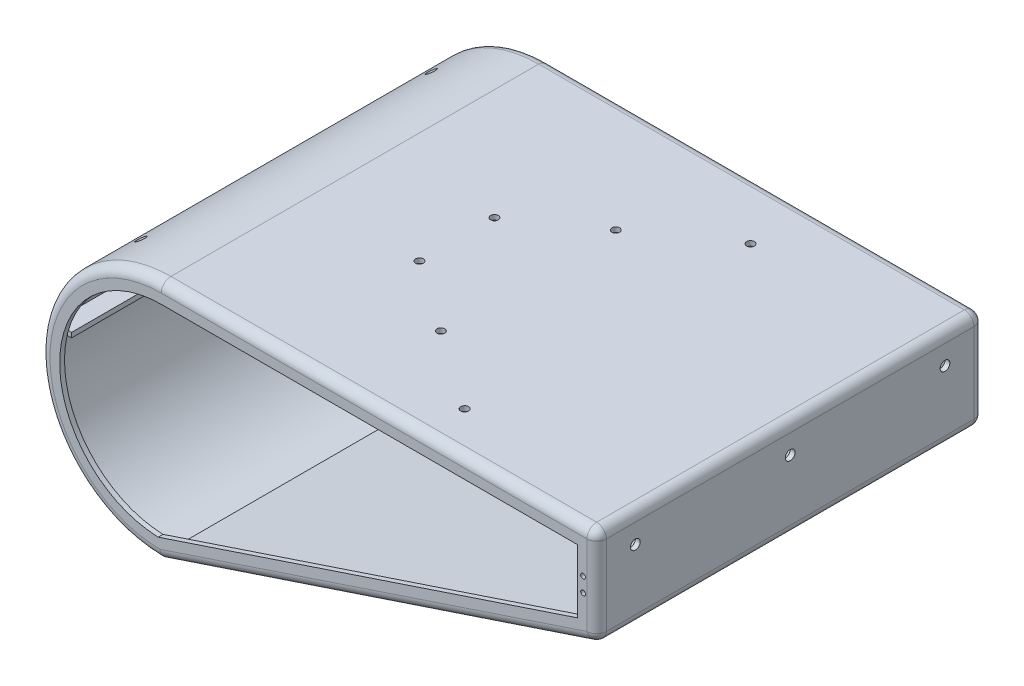
SolidWorks part; units mm, degrees
material "Acrylic (Medium-high impact)"
ref_plane "Front Plane" through (0, 0, 0) normal (0, 0, 1) x (1, 0, 0)
ref_plane "Top Plane" through (0, 0, 0) normal (0, 1, 0) x (1, 0, 0)
ref_plane "Right Plane" through (0, 0, 0) normal (1, 0, 0) x (0, 0, -1)
sketch "Sketch1" plane through (0, 0, 0) normal (0, 0, 1) x (1, 0, 0)
  line L1 (-100, 0) -> (350, 0)
  line L4 (350, 0) -> (350, -100)
  line L5 (-100, -250) -> (350, -100)
  arc A0 (-100, 0) -> (-100, -250) centre (-100, -125) ccw
  dimension "D2" = 125
  dimension "D1" = 350
  dimension "D3" = 100
  dimension "D4" = 100
extrude "Boss-Extrude1" add sketch "Sketch1" along normal blind 400 contours L1 L4 L5 A0
fillet "Fillet1" radius 10 10 edges at (-225, -125, 0) (-225, -125, 400) (125, 0, 0) (125, -175, 0) (350, -50, 0) (350, -100, 200) (350, 0, 200) (350, -50, 400) (125, -175, 400) (125, 0, 400)
ref_plane "Plane2" through (0, 0, 5) normal (0, 0, -1) x (-1, 0, 0)
sketch "Sketch7" plane through (0, 0, 5) normal (0, 0, -1) x (-1, 0, 0)
  line L9 (-345, -96.3962) -> (100.8033, -244.9973)
  line L10 (-345, -5) -> (-345, -96.3962)
  line L11 (100, -5) -> (-345, -5)
  line L12 (-345, -96.3962) -> (100.8033, -244.9973)
  line L13 (-345, -5) -> (-345, -96.3962)
  line L14 (100, -5) -> (-345, -5)
  arc A5 (100.8033, -244.9973) -> (100, -5) centre (100, -125) ccw
  arc A6 (100.8033, -244.9973) -> (100, -5) centre (100, -125) ccw
  dimension "D1" = 5
sketch "Sketch4" plane through (350, 0, 0) normal (1, 0, 0) x (0, 0, -1)
  line L0 (-390, -30) -> (-10, -30) construction
  line L4 (-10, -10) -> (-390, -10) construction
  line L5 (-390, -10) -> (-390, -92.7924) construction
  line L6 (-10, -92.7924) -> (-10, -10) construction
  circle A0 centre (-200, -30) radius 5
  circle A1 centre (-360, -30) radius 5
  circle A2 centre (-40, -30) radius 5
  dimension "D1" = 10
  dimension "D2" = 20
  dimension "D3" = 30
  dimension "D4" = 30
sketch "Sketch6" plane through (0, 0, 0) normal (0, 1, 0) x (1, 0, 0)
  line L3 (-37.2545, -10) -> (-37.2545, -390) construction
  line L4 (340, -10) -> (-100, -10) construction
  line L5 (-100, -390) -> (340, -390) construction
  arc A0 (8.0546, -173.8432) -> (7.7455, -225.9808) centre (22.7455, -200) ccw construction
  circle A3 centre (88.3792, -118.6576) radius 4
  circle A4 centre (88.3792, -299.4355) radius 4
  circle A5 centre (14.6483, -170.2692) radius 4
  circle A6 centre (14.6483, -247.8239) radius 4
  circle A7 centre (170.3024, -356.7817) radius 4
  circle A8 centre (170.3024, -61.3114) radius 4
  circle A9 centre (14.6483, -247.8239) radius 2.5 construction
  circle A10 centre (88.3792, -118.6576) radius 2.5 construction
  circle A11 centre (88.3792, -299.4355) radius 2.5 construction
  circle A12 centre (170.3024, -356.7817) radius 2.5 construction
  circle A13 centre (170.3024, -61.3114) radius 2.5 construction
  point P18 (22.7455, -200)
  dimension "D6" = 8
  dimension "D1" = 170.2692
  dimension "D7" = 7.5
extrude "Cut-Extrude1" cut sketch "Sketch7" against normal blind 390
sketch "Sketch8" plane through (0, 0, 400) normal (0, 0, 1) x (1, 0, 0)
  line L6 (-103.1076, -229.954) -> (330, -85.5848)
  line L7 (330, -85.5848) -> (330, -20)
  line L8 (330, -20) -> (-100, -20)
  line L9 (-103.1076, -229.954) -> (330, -85.5848)
  line L10 (330, -85.5848) -> (330, -20)
  line L11 (330, -20) -> (-100, -20)
  arc A2 (-100, -20) -> (-103.1076, -229.954) centre (-100, -125) ccw
  arc A3 (-100, -20) -> (-103.1076, -229.954) centre (-100, -125) ccw
  dimension "D1" = 10
extrude "Cut-Extrude2" cut sketch "Sketch8" against normal blind 10
extrude "Cut-Extrude3" cut sketch "Sketch6" against normal blind 10
sketch "Sketch9" plane through (0, 0, 5) normal (0, 0, -1) x (-1, 0, 0)
  line L0 (-345, -96.3962) -> (216.5411, -96.3962) construction
  line L1 (216.5411, -96.3962) -> (197.6557, -96.3962)
  line L2 (197.6557, -96.3962) -> (197.6557, -101.3962)
  line L3 (197.6557, -101.3962) -> (217.6557, -101.3962)
  line L5 (-325, -96.3962) -> (-325, -103.0629)
  line L6 (-345, -96.3962) -> (100.8033, -244.9973) construction
  line L7 (-325, -96.3962) -> (-345, -96.3962)
  line L8 (-345, -96.3962) -> (-325, -103.0629)
  line L10 (216.5411, -96.3962) -> (218.5411, -96.3962)
  line L11 (218.5411, -96.3962) -> (218.5411, -101.3962)
  line L12 (218.5411, -101.3962) -> (217.6557, -101.3962)
  arc A0 (100.8033, -244.9973) -> (100, -5) centre (100, -125) ccw construction
  dimension "D1" = 5
  dimension "D2" = 20
  dimension "D3" = 20
  dimension "D4" = 2
extrude "Boss-Extrude2" add sketch "Sketch9" against normal blind 390
extrude "Cut-Extrude4" cut sketch "Sketch4" against normal blind 10
sketch "Sketch10" plane through (0, 0, 400) normal (0, 0, 1) x (1, 0, 0)
  line L0 (330, -85.5848) -> (330, -20) construction
  line L1 (336, -45.2924) -> (336, -60.2924) construction
  line L2 (330, -20) -> (330, -85.5848) construction
  circle A0 centre (336, -45.2924) radius 2.5
  circle A1 centre (336, -60.2924) radius 2.5
  point P13 (330, -52.7924)
  point P14 (336, -52.7924)
  dimension "D1" = 5
  dimension "D2" = 15
  dimension "D3" = 6
extrude "Cut-Extrude5" cut sketch "Sketch10" against normal blind 10
sketch "Sketch11" plane through (0, 0, 400) normal (0, 0, 1) x (1, 0, 0)
  line L0 (-225, -125) -> (-100, -125) construction
  arc A1 (-100, 0) -> (-100, -250) centre (-100, -125) ccw construction
ref_plane "Plane3" through (-45.8653, 65.5024, 0) normal (-0.5736, 0.8192, 0) x (0, 0, -1)
sketch "Sketch12" plane through (-45.8653, 65.5024, 0) normal (-0.5736, 0.8192, 0) x (0, 0, -1)
  line L0 (-390, 81.9152) -> (-10, 81.9152) construction
  line L1 (-350, 152.8988) -> (-50, 152.8988) construction
  line L2 (-390, 278.6123) -> (-390, 81.9152) construction
  circle A0 centre (-50, 152.8988) radius 5
  circle A1 centre (-350, 152.8988) radius 5
  point P5 (-200, 81.9152)
  point P7 (-200, 152.8988)
  dimension "D1" = 10
  dimension "D2" = 10
  dimension "D3" = 300
extrude "Cut-Extrude6" cut sketch "Sketch12" against normal blind 20
sketch "Sketch13" plane through (65, -195, 0) normal (0.3162, -0.9487, 0) x (0.9487, 0.3162, 0)
  line L1 (0, 0) -> (0, 399.8115) construction
  circle A0 centre (0, 199.9058) radius 15
  dimension "D1" = 30
extrude "Boss-Extrude3" add sketch "Sketch13" along normal blind 1.5
sketch "Sketch14" plane through (65.4743, -196.423, 0) normal (0.3162, -0.9487, 0) x (0.9487, 0.3162, 0)
  circle A0 centre (0, 199.9058) radius 13
  circle A1 centre (0, 199.9058) radius 15 construction
  circle A2 centre (0, 199.9058) radius 15 construction
  dimension "D1" = 2
extrude "Cut-Extrude7" cut sketch "Sketch14" against normal blind 21 and the other way blind 11
ref_plane "Plane4" through (-44.1268, 64.5763, 0) normal (-0.5642, 0.8256, 0) x (0.8256, 0.5642, 0)
